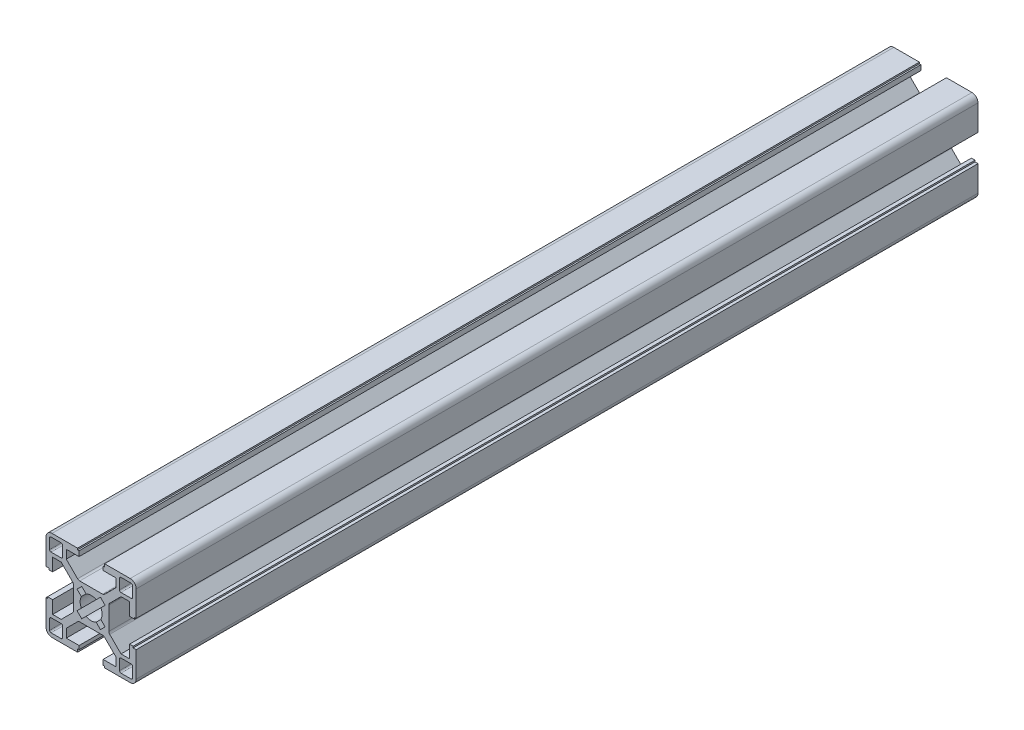
SolidWorks part; units mm, degrees
material "6061-T6 (SS)"
ref_plane "Front Plane" through (0, 0, 0) normal (0, 0, 1) x (1, 0, 0)
ref_plane "Top Plane" through (0, 0, 0) normal (0, 1, 0) x (1, 0, 0)
ref_plane "Right Plane" through (0, 0, 0) normal (1, 0, 0) x (0, 0, -1)
sketch "Sketch1" plane through (0, 0, 0) normal (0, 0, 1) x (1, 0, 0)
  line L0 (-4.5, 15) -> (-4.5, 14.5)
  line L1 (13, -15) -> (4.5, -15)
  line L2 (15, -13) -> (15, -4.5)
  line L3 (13, 15) -> (4.5, 15)
  line L4 (-15, -13) -> (-15, -4.5)
  line L5 (15, -15) -> (-15, 15) construction
  line L6 (15, 15) -> (-15, -15) construction
  line L7 (-4.5, 14.5) -> (-4, 14.5)
  line L8 (-4, 14.5) -> (-4, 12.8)
  line L9 (-4, 12.8) -> (-8.25, 12.8)
  line L10 (-8.25, 12.8) -> (-8.25, 9.95)
  line L11 (-8.25, 9.95) -> (-4.4929, 6.1929)
  line L12 (-3.7858, 5.9) -> (3.7858, 5.9)
  line L13 (4.4929, 6.1929) -> (8.25, 9.95)
  line L14 (8.25, 9.95) -> (8.25, 12.8)
  line L15 (8.25, 12.8) -> (4, 12.8)
  line L16 (4, 12.8) -> (4, 14)
  line L17 (4, 14) -> (4.5, 14)
  line L18 (4.5, 14) -> (4.5, 15)
  line L19 (0, 0) -> (0, 16.8698) construction
  line L20 (-4.5, 15) -> (-13, 15)
  line L21 (12.8, 8.25) -> (9.95, 8.25)
  line L22 (9.95, 8.25) -> (6.1929, 4.4929)
  line L23 (5.9, 3.7858) -> (5.9, -3.7858)
  line L24 (6.1929, -4.4929) -> (9.95, -8.25)
  line L25 (9.95, -8.25) -> (12.8, -8.25)
  line L26 (12.8, -8.25) -> (12.8, -4)
  line L27 (12.8, 4) -> (12.8, 8.25)
  line L28 (12.8, -4) -> (14, -4)
  line L29 (14, -4) -> (14, -4.5)
  line L30 (14, -4.5) -> (15, -4.5)
  line L31 (14.5, 4) -> (12.8, 4)
  line L32 (14.5, 4.5) -> (14.5, 4)
  line L33 (15, 4.5) -> (14.5, 4.5)
  line L34 (8.25, -12.8) -> (8.25, -9.95)
  line L35 (8.25, -9.95) -> (4.4929, -6.1929)
  line L36 (3.7858, -5.9) -> (-3.7858, -5.9)
  line L37 (-4.4929, -6.1929) -> (-8.25, -9.95)
  line L38 (-8.25, -9.95) -> (-8.25, -12.8)
  line L39 (-8.25, -12.8) -> (-4, -12.8)
  line L40 (4, -12.8) -> (8.25, -12.8)
  line L41 (-4, -12.8) -> (-4, -14)
  line L42 (-4, -14) -> (-4.5, -14)
  line L43 (-4.5, -14) -> (-4.5, -15)
  line L44 (4, -14.5) -> (4, -12.8)
  line L45 (4.5, -14.5) -> (4, -14.5)
  line L46 (4.5, -15) -> (4.5, -14.5)
  line L47 (-12.8, -8.25) -> (-9.95, -8.25)
  line L48 (-9.95, -8.25) -> (-6.1929, -4.4929)
  line L49 (-5.9, -3.7858) -> (-5.9, 3.7858)
  line L50 (-6.1929, 4.4929) -> (-9.95, 8.25)
  line L51 (-9.95, 8.25) -> (-12.8, 8.25)
  line L52 (-12.8, 8.25) -> (-12.8, 4)
  line L53 (-12.8, -4) -> (-12.8, -8.25)
  line L54 (-12.8, 4) -> (-14, 4)
  line L55 (-14, 4) -> (-14, 4.5)
  line L56 (-14, 4.5) -> (-15, 4.5)
  line L57 (-14.5, -4) -> (-12.8, -4)
  line L58 (-14.5, -4.5) -> (-14.5, -4)
  line L59 (-15, -4.5) -> (-14.5, -4.5)
  line L60 (15, 4.5) -> (15, 13)
  line L61 (-15, 4.5) -> (-15, 13)
  line L62 (-4.5, -15) -> (-13, -15)
  line L63 (13.3, -9.45) -> (9.95, -9.45)
  line L64 (9.95, 13.8) -> (13.3, 13.8)
  line L65 (9.45, 13.3) -> (9.45, 9.95)
  line L66 (9.95, 9.45) -> (13.3, 9.45)
  line L67 (13.8, 13.3) -> (13.8, 9.95)
  line L68 (13.8, -9.95) -> (13.8, -13.3)
  line L69 (13.3, -13.8) -> (9.95, -13.8)
  line L70 (9.45, -9.95) -> (9.45, -13.3)
  line L71 (-9.45, -13.3) -> (-9.45, -9.95)
  line L72 (-9.95, -13.8) -> (-13.3, -13.8)
  line L73 (-13.8, -13.3) -> (-13.8, -9.95)
  line L74 (-9.95, -9.45) -> (-13.3, -9.45)
  line L75 (-13.3, 9.45) -> (-9.95, 9.45)
  line L76 (-13.8, 9.95) -> (-13.8, 13.3)
  line L77 (-13.3, 13.8) -> (-9.95, 13.8)
  line L78 (-9.45, 9.95) -> (-9.45, 13.3)
  line L79 (-1.6831, -3.2388) -> (-3.1113, -4.6669)
  line L80 (3.1113, 4.6669) -> (4.6669, 3.1113)
  line L81 (4.6669, 3.1113) -> (3.2388, 1.6831)
  line L82 (-3.1113, -4.6669) -> (-4.6669, -3.1113)
  line L83 (-4.6669, -3.1113) -> (-3.2388, -1.6831)
  line L85 (3.1113, -4.6669) -> (4.6669, -3.1113)
  line L86 (3.1113, -4.6669) -> (1.6831, -3.2388)
  line L87 (-4.6669, 3.1113) -> (-3.1113, 4.6669)
  line L88 (-3.1113, 4.6669) -> (-1.6831, 3.2388)
  line L93 (3.2388, -1.6831) -> (4.6669, -3.1113)
  line L95 (1.6831, 3.2388) -> (3.1113, 4.6669)
  line L98 (-3.2388, 1.6831) -> (-4.6669, 3.1113)
  arc A0 (-3.2388, 1.6831) -> (-3.2388, -1.6831) centre (0, 0) ccw
  arc A1 (13, 15) -> (15, 13) centre (13, 13) cw
  arc A2 (15, -13) -> (13, -15) centre (13, -13) cw
  arc A3 (-13, -15) -> (-15, -13) centre (-13, -13) cw
  arc A4 (-15, 13) -> (-13, 15) centre (-13, 13) cw
  arc A5 (-6.1929, 4.4929) -> (-5.9, 3.7858) centre (-6.9, 3.7858) cw
  arc A6 (9.95, 13.8) -> (9.45, 13.3) centre (9.95, 13.3) ccw
  arc A7 (-5.9, -3.7858) -> (-6.1929, -4.4929) centre (-6.9, -3.7858) cw
  arc A8 (-4.4929, -6.1929) -> (-3.7858, -5.9) centre (-3.7858, -6.9) cw
  arc A9 (9.45, 9.95) -> (9.95, 9.45) centre (9.95, 9.95) ccw
  arc A10 (13.8, 9.95) -> (13.3, 9.45) centre (13.3, 9.95) cw
  arc A11 (13.8, 13.3) -> (13.3, 13.8) centre (13.3, 13.3) ccw
  arc A12 (13.8, -9.95) -> (13.3, -9.45) centre (13.3, -9.95) ccw
  arc A13 (13.3, -13.8) -> (13.8, -13.3) centre (13.3, -13.3) ccw
  arc A14 (9.95, -13.8) -> (9.45, -13.3) centre (9.95, -13.3) cw
  arc A15 (9.95, -9.45) -> (9.45, -9.95) centre (9.95, -9.95) ccw
  arc A16 (1.6831, 3.2388) -> (-1.6831, 3.2388) centre (0, 0) ccw
  arc A17 (-9.95, -13.8) -> (-9.45, -13.3) centre (-9.95, -13.3) ccw
  arc A18 (-13.8, -13.3) -> (-13.3, -13.8) centre (-13.3, -13.3) ccw
  arc A19 (-13.8, -9.95) -> (-13.3, -9.45) centre (-13.3, -9.95) cw
  arc A20 (-9.45, -9.95) -> (-9.95, -9.45) centre (-9.95, -9.95) ccw
  arc A21 (1.6831, 3.2388) -> (-1.6831, 3.2388) centre (0, 0) ccw
  arc A22 (-13.8, 9.95) -> (-13.3, 9.45) centre (-13.3, 9.95) ccw
  arc A23 (-13.3, 13.8) -> (-13.8, 13.3) centre (-13.3, 13.3) ccw
  arc A24 (-9.95, 13.8) -> (-9.45, 13.3) centre (-9.95, 13.3) cw
  arc A25 (-9.95, 9.45) -> (-9.45, 9.95) centre (-9.95, 9.95) ccw
  arc A26 (3.2388, -1.6831) -> (3.2388, 1.6831) centre (0, 0) ccw
  arc A27 (3.7858, -5.9) -> (4.4929, -6.1929) centre (3.7858, -6.9) cw
  arc A28 (6.1929, -4.4929) -> (5.9, -3.7858) centre (6.9, -3.7858) cw
  arc A29 (5.9, 3.7858) -> (6.1929, 4.4929) centre (6.9, 3.7858) cw
  arc A30 (4.4929, 6.1929) -> (3.7858, 5.9) centre (3.7858, 6.9) cw
  arc A31 (-3.7858, 5.9) -> (-4.4929, 6.1929) centre (-3.7858, 6.9) cw
  arc A32 (3.2388, -1.6831) -> (3.2388, 1.6831) centre (0, 0) ccw
  arc A33 (-3.2388, 1.6831) -> (-3.2388, -1.6831) centre (0, 0) ccw
  arc A34 (-1.6831, -3.2388) -> (1.6831, -3.2388) centre (0, 0) ccw
  arc A35 (-1.6831, -3.2388) -> (1.6831, -3.2388) centre (0, 0) ccw
  point P0 (0, 0)
  point P70 (0, 0)
  point P135 (0, 0)
  point P144 (4.2, 5.9)
  point P147 (-4.2, 5.9)
  point P151 (0, 0)
  point P154 (3.8891, 3.8891)
  point P159 (0, 0)
  point P162 (3.8891, -3.8891)
  dimension "D18" = 7.3
  dimension "D20" = 2
  dimension "D21" = 1
  dimension "D22" = 1.2
  dimension "D23" = 30
  dimension "D28" = 0.5
  dimension "D1" = 30
  dimension "D2" = 30
  dimension "D3" = 8
  dimension "D4" = 4
  dimension "D5" = 9
  dimension "D6" = 4.5
  dimension "D7" = 1
  dimension "D8" = 0.5
  dimension "D9" = 16.5
  dimension "D10" = 8.25
  dimension "D11" = 2.2
  dimension "D12" = 2.2
  dimension "D13" = 9.1
  dimension "D14" = 2.4042
  dimension "D16" = 45
  dimension "D17" = 45
  dimension "D25" = 1.2
  dimension "D26" = 1.2
  dimension "D27" = 1.2
  dimension "D19" = 4
extrude "Boss-Extrude1" add sketch "Sketch1" along normal blind 280 contours A0 | L75 A25 L78 A24 L77 A23 L76 A22 | L71 A20 L74 A19 L73 A18 L72 A17 | L63 A15 L70 A14 L69 A13 L68 A12 | L67 A11 L64 A6 L65 A9 L66 A10 | L36 A8 L37 L38 L39 L41 L42 L43 L62 A3 L4 L59 L58 L57 L53 L47 L48 A7 L49 A5 L50 L51 L52 L54 L55 L56 L61 A4 L20 L0 L7 L8 L9 L10 L11 A31 L12 A30 L13 L14 L15 L16 L17 L18 L3 A1 L60 L33 L32 L31 L27 L21 L22 A29 L23 A28 L24 L25 L26 L28 L29 L30 L2 A2 L1 L46 L45 L44 L40 L34 L35 A27 region at (11.625, -11.625, 0) region at (11.625, 11.625, 0) region at (-11.625, -11.625, 0) region at (-11.625, 11.625, 0) region at (0, 0, 0)
